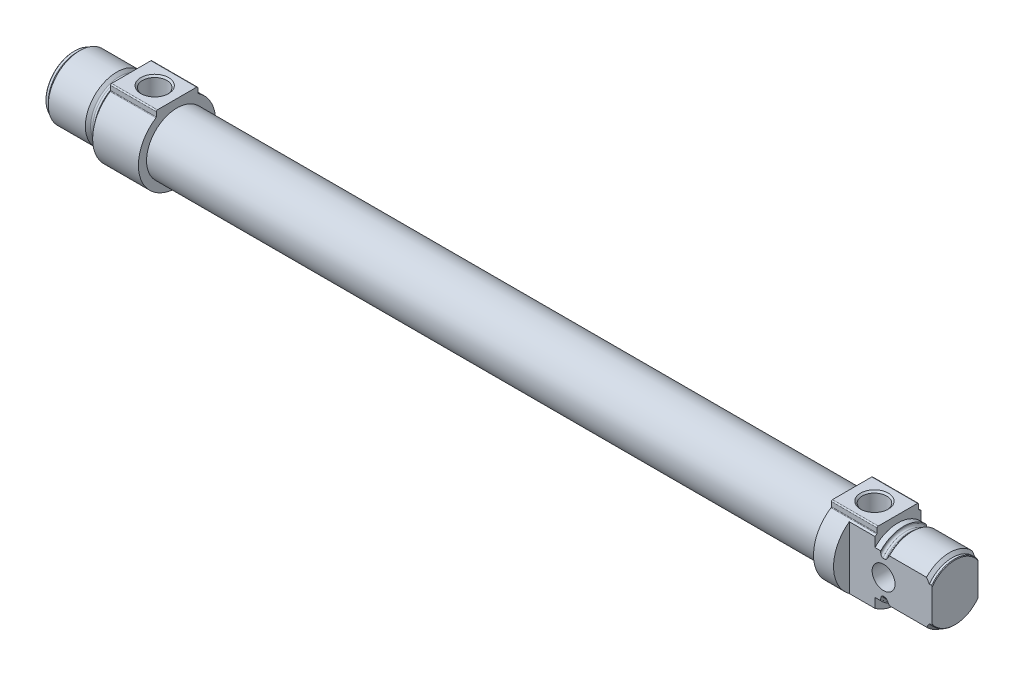
SolidWorks part; units mm, degrees
ref_plane "Ebene vorne" through (0, 0, 0) normal (0, 0, 1) x (1, 0, 0)
ref_plane "Ebene oben" through (0, 0, 0) normal (0, 1, 0) x (1, 0, 0)
ref_plane "Ebene rechts" through (0, 0, 0) normal (1, 0, 0) x (0, 0, -1)
sketch "Skizze1" plane through (0, 0, 0) normal (0, 0, 1) x (1, 0, 0)
  line L0 (0, 0) -> (0, 9.8)
  line L1 (0, 9.8) -> (0.2, 10)
  line L2 (0.2, 10) -> (1, 10)
  line L3 (1, 10) -> (2, 11)
  line L4 (2, 11) -> (14.95, 11)
  line L5 (14.95, 11) -> (15.8657, 10.0843)
  line L6 (16.4314, 9.85) -> (17.2, 9.85)
  line L7 (18, 10.65) -> (18, 11)
  line L8 (18, 11) -> (20, 11)
  line L9 (20, 11) -> (20, 0)
  line L10 (20, 0) -> (0, 0)
  line L11 (20, 0) -> (0, 0) construction
  arc A0 (15.8657, 10.0843) -> (16.4314, 9.85) centre (16.4314, 10.65) ccw
  arc A1 (17.2, 9.85) -> (18, 10.65) centre (17.2, 10.65) ccw
revolve "Rotation1" add sketch "Skizze1" angle 360 about L11 reverse direction yes
cosmetic thread "Gewindedarstellung1" parameters "D1"=13.87, "D2"=20.16
ref_plane "Ebene1" through (28.7, 0, 0) normal (1, 0, 0) x (0, 0, -1)
ref_plane "Ebene2" through (10.5, 0, 0) normal (1, 0, 0) x (0, 0, -1)
ref_plane "Ebene3" through (0, -14, 0) normal (0, 1, 0) x (1, 0, 0)
ref_plane "Ebene4" through (0, 13, 0) normal (0, 1, 0) x (1, 0, 0)
ref_plane "Ebene5" through (0, 0, 0) normal (0, 1, 0) x (1, 0, 0)
ref_plane "Ebene6" through (0, 0, 0) normal (0, 1, 0) x (1, 0, 0)
ref_plane "Ebene7" through (20, 0, 0) normal (1, 0, 0) x (0, 0, -1)
ref_plane "Ebene8" through (20, 0, 0) normal (1, 0, 0) x (0, 0, -1)
ref_plane "Ebene9" through (33, 0, 0) normal (1, 0, 0) x (0, 0, -1)
ref_plane "Ebene10" through (24.5, 0, 0) normal (1, 0, 0) x (0, 0, -1)
ref_plane "Ebene11" through (44.5, 0, 0) normal (1, 0, 0) x (0, 0, -1)
sketch "Skizze2" plane through (20, 0, 0) normal (1, 0, 0) x (0, 0, -1)
  line L0 (7.25, 11.5515) -> (7.25, 13.1)
  line L1 (6.85, 13.5) -> (-6.85, 13.5)
  line L2 (-7.25, 13.1) -> (-7.25, 11.5515)
  arc A0 (-7.3859, 11.3004) -> (7.3859, 11.3004) centre (0, 0) ccw
  arc A1 (7.3859, 11.3004) -> (7.25, 11.5515) centre (7.55, 11.5515) cw
  arc A2 (7.25, 13.1) -> (6.85, 13.5) centre (6.85, 13.1) ccw
  arc A3 (-6.85, 13.5) -> (-7.25, 13.1) centre (-6.85, 13.1) ccw
  arc A4 (-7.25, 11.5515) -> (-7.3859, 11.3004) centre (-7.55, 11.5515) cw
extrude "Aufsatz-Linear austragen1" add sketch "Skizze2" along normal blind 16
ref_plane "Ebene12" through (32.5, 0, 0) normal (1, 0, 0) x (0, 0, -1)
ref_plane "Ebene13" through (0, 0, 0) normal (0, 0, 1) x (1, 0, 0)
ref_plane "Ebene14" through (0, 0, -8.5) normal (0, 0, 1) x (1, 0, 0)
ref_plane "Ebene15" through (0, 0, 0) normal (0, 1, 0) x (1, 0, 0)
ref_plane "Ebene16" through (0, 6.9, 0) normal (0, 1, 0) x (1, 0, 0)
ref_plane "Ebene17" through (0, 0, -6.6) normal (0, 0, 1) x (1, 0, 0)
ref_plane "Ebene18" through (0, 0, 0) normal (0, 1, 0) x (1, 0, 0)
ref_plane "Ebene19" through (0, 6.9, 0) normal (0, 1, 0) x (1, 0, 0)
ref_plane "Ebene20" through (0, 7.8206, -1.379) normal (0, 0.9848, -0.1736) x (1, 0, 0)
ref_plane "Ebene21" through (0, 6.3434, -1.1185) normal (0, 0.9848, -0.1736) x (1, 0, 0)
sketch "Skizze3" plane through (0, 0, 0) normal (0, 0, 1) x (1, 0, 0)
  line L0 (36, 0) -> (36, 10.65)
  line L1 (36, 10.65) -> (272, 10.65)
  line L2 (272, 10.65) -> (272, 0)
  line L3 (272, 0) -> (36, 0)
  line L4 (272, 0) -> (36, 0) construction
revolve "Rotation2" add sketch "Skizze3" angle 360 about L4 reverse direction yes
ref_plane "Ebene22" through (272, 0, 0) normal (1, 0, 0) x (0, 0, -1)
sketch "Skizze4" plane through (272, 0, 0) normal (1, 0, 0) x (0, 0, -1)
  line L0 (7.25, 11.5515) -> (7.25, 13.1)
  line L1 (6.85, 13.5) -> (-6.85, 13.5)
  line L2 (-7.25, 13.1) -> (-7.25, 11.5515)
  arc A0 (-7.3859, 11.3004) -> (7.3859, 11.3004) centre (0, 0) ccw
  arc A1 (7.3859, 11.3004) -> (7.25, 11.5515) centre (7.55, 11.5515) cw
  arc A2 (7.25, 13.1) -> (6.85, 13.5) centre (6.85, 13.1) ccw
  arc A3 (-6.85, 13.5) -> (-7.25, 13.1) centre (-6.85, 13.1) ccw
  arc A4 (-7.25, 11.5515) -> (-7.3859, 11.3004) centre (-7.55, 11.5515) cw
extrude "Aufsatz-Linear austragen2" add sketch "Skizze4" along normal blind 16
ref_plane "Ebene23" through (275.8, 0, 0) normal (1, 0, 0) x (0, 0, -1)
ref_plane "Ebene24" through (275.5, 0, 0) normal (1, 0, 0) x (0, 0, -1)
ref_plane "Ebene25" through (0, 0, 6.6) normal (0, 0, 1) x (1, 0, 0)
ref_plane "Ebene26" through (0, 0, 0) normal (0, 1, 0) x (1, 0, 0)
ref_plane "Ebene27" through (0, 6.9, 0) normal (0, 1, 0) x (1, 0, 0)
ref_plane "Ebene28" through (0, 7.8206, 1.379) normal (0, 0.9848, 0.1736) x (1, 0, 0)
ref_plane "Ebene29" through (0, 6.3434, 1.1185) normal (0, 0.9848, 0.1736) x (1, 0, 0)
ref_plane "Ebene30" through (335, 0, 0) normal (1, 0, 0) x (0, 0, -1)
sketch "Skizze5" plane through (0, 0, 0) normal (0, 0, 1) x (1, 0, 0)
  line L0 (288, 0) -> (288, 11)
  line L1 (288, 11) -> (290, 11)
  line L2 (290, 11) -> (290, 10.65)
  line L3 (290.8, 9.85) -> (291.5686, 9.85)
  line L4 (292.1343, 10.0843) -> (293.05, 11)
  line L5 (293.05, 11) -> (306, 11)
  line L6 (306, 11) -> (307, 10)
  line L7 (307, 10) -> (307.8, 10)
  line L8 (307.8, 10) -> (308, 9.8)
  line L9 (308, 9.8) -> (308, 0)
  line L10 (308, 0) -> (288, 0)
  line L11 (308, 0) -> (288, 0) construction
  arc A0 (290, 10.65) -> (290.8, 9.85) centre (290.8, 10.65) ccw
  arc A1 (291.5686, 9.85) -> (292.1343, 10.0843) centre (291.5686, 10.65) ccw
revolve "Rotation3" add sketch "Skizze5" angle 360 about L11 reverse direction yes
cosmetic thread "Gewindedarstellung2" parameters "D1"=12.87, "D2"=20.16
ref_plane "Ebene31" through (322, 0, 0) normal (1, 0, 0) x (0, 0, -1)
ref_plane "Ebene32" through (330.5, 0, 0) normal (1, 0, 0) x (0, 0, -1)
ref_plane "Ebene33" through (310.5, 0, 0) normal (1, 0, 0) x (0, 0, -1)
sketch "Skizze6" plane through (0, 0, 0) normal (0, 1, 0) x (1, 0, 0)
  line L0 (279, 24) -> (279, 8)
  line L1 (279, 8) -> (308, 8)
  line L2 (308, 8) -> (308, -8)
  line L3 (308, -8) -> (279, -8)
  line L4 (279, -8) -> (279, -24)
  line L5 (279, -24) -> (324, -24)
  line L6 (324, -24) -> (324, 24)
  line L7 (324, 24) -> (279, 24)
extrude "Schnitt-Linear austragen1" cut sketch "Skizze6" along normal blind 13.5 and the other way blind 13.5
ref_plane "Ebene34" through (291, 0, 0) normal (1, 0, 0) x (0, 0, -1)
hole_wizard "Bohrung1" positions "Skizze8" profile "Skizze7" legacy
sketch "Skizze8" plane through (0, 0, -8) normal (0, 0, -1) x (-1, 0, 0)
  point P0 (-291, 0)
sketch "Skizze7" plane through (291, 0, -8) normal (1, 0, 0) x (0, 1, 0)
  line L0 (0, 0) -> (0, 16)
  line L1 (0, 16) -> (4, 16)
  line L2 (4, 16) -> (4, 0)
  line L3 (4, 0) -> (0, 0)
  line L4 (0, 110) -> (0, -10) construction
  dimension "Durchmesser" = 8
  dimension "Tiefe" = 16
hole_wizard "Bohrung2" positions "Skizze10" profile "Skizze9" legacy
sketch "Skizze10" plane through (0, 13.5, 0) normal (0, 1, 0) x (1, 0, 0)
  point P0 (28.2, 0)
sketch "Skizze9" plane through (28.2, 13.5, 0) normal (1, 0, 0) x (0, 0, 1)
  line L0 (0, 0) -> (0, 13.5)
  line L1 (0, 13.5) -> (4.283, 13.5)
  line L2 (4.283, 13.5) -> (4.283, 0.581)
  line L3 (4.283, 0.581) -> (4.864, 0)
  line L4 (4.864, 0) -> (0, 0)
  line L5 (0, -6.4453) -> (0, 115.525) construction
  line L6 (-4.283, 0.581) -> (-4.864, 0) construction
  dimension "Durchmesser" = 8.566
  dimension "Tiefe" = 13.5
  dimension "Senkwinkel1" = 90
  dimension "Senkdurchmesser3" = 9.728
cosmetic thread "Gewindedarstellung3" parameters "D1"=9.5, "D2"=9.728
hole_wizard "Bohrung3" positions "Skizze12" profile "Skizze11" legacy
sketch "Skizze12" plane through (0, 13.5, 0) normal (0, 1, 0) x (1, 0, 0)
  point P0 (279.8, 0)
sketch "Skizze11" plane through (279.8, 13.5, 0) normal (1, 0, 0) x (0, 0, 1)
  line L0 (0, 0) -> (0, 18.4728)
  line L1 (0, 18.4728) -> (4.283, 16)
  line L2 (4.283, 16) -> (4.283, 0.581)
  line L3 (4.283, 0.581) -> (4.864, 0)
  line L4 (4.864, 0) -> (0, 0)
  line L5 (0, -14.3089) -> (0, 102.4216) construction
  line L6 (0, 18.4728) -> (-4.283, 16) construction
  line L7 (-4.283, 0.581) -> (-4.864, 0) construction
  dimension "Durchmesser" = 8.566
  dimension "Tiefe" = 16
  dimension "Senkdurchmesser1" = 9.728
  dimension "Senkwinkel1" = 90
  dimension "Spitzenwinkel" = 120
cosmetic thread "Gewindedarstellung4" parameters "D1"=8, "D2"=9.728
sketch "Skizze13" plane through (0, 0, 0) normal (0, 0, 1) x (1, 0, 0)
  line L0 (-4, 0) -> (-4, 4)
  line L1 (-4, 4) -> (50.3, 4)
  line L2 (50.3, 4) -> (50.3, 10)
  line L3 (50.3, 10) -> (255.3, 10)
  line L4 (255.3, 10) -> (255.3, 0)
  line L5 (255.3, 0) -> (-4, 0)
  line L6 (255.3, 0) -> (-4, 0) construction
revolve "Schnitt-Rotation1" cut sketch "Skizze13" angle 360 about L6 reverse direction yes
ref_plane "Ebene35" through (-4, 0, 0) normal (1, 0, 0) x (0, 0, -1)
ref_plane "Ebene36" through (0, 13.5, 0) normal (0, 1, 0) x (1, 0, 0)
ref_plane "Ebene37" through (6.5, 0, 0) normal (1, 0, 0) x (0, 0, -1)
ref_plane "Ebene38" through (0, 0, 0) normal (1, 0, 0) x (0, 0, -1)
ref_plane "Ebene39" through (20, 0, 0) normal (1, 0, 0) x (0, 0, -1)
ref_plane "Ebene40" through (288, 0, 0) normal (1, 0, 0) x (0, 0, -1)
ref_plane "Ebene41" through (20, 0, 0) normal (1, 0, 0) x (0, 0, -1)
ref_plane "Ebene42" through (0, 13.5, 0) normal (0, 1, 0) x (1, 0, 0)
ref_plane "Ebene43" through (45.5, 0, 0) normal (1, 0, 0) x (0, 0, -1)
ref_plane "Ebene44" through (262.5, 0, 0) normal (1, 0, 0) x (0, 0, -1)
ref_plane "Ebene45" through (0, 0, 0) normal (0, 0, 1) x (1, 0, 0)
ref_plane "Ebene46" through (20, 0, 0) normal (1, 0, 0) x (0, 0, -1)
ref_plane "Ebene47" through (0, 13.5, 0) normal (0, 1, 0) x (1, 0, 0)
ref_plane "FDT_FRONT XY" through (20, 0, 0) normal (1, 0, 0) x (0, 0, -1)
ref_plane "FDT_FRONT XZ" through (0, 0, 0) normal (0, -1, 0) x (-1, 0, 0)
ref_plane "FDT_FRONT YZ" through (0, 0, 0) normal (0, 0, -1) x (-1, 0, 0)
ref_axis "FDT_FRONT X" through (20, 0, 80.9) along (0, 0, -1)
ref_axis "FDT_FRONT Y" through (20, -50, 0) along (0, 1, 0)
ref_axis "FDT_FRONT Z" through (80.9, 0, 0) along (-1, 0, 0)
sketch3d "FDT_FRONT"
  point P0 (20, 0, 0)
ref_plane "FDT_QSFRONT XY" through (0, 13.5, 0) normal (0, 1, 0) x (1, 0, 0)
ref_plane "FDT_QSFRONT XZ" through (28.2, 0, 0) normal (-1, 0, 0) x (0, 0, 1)
ref_plane "FDT_QSFRONT YZ" through (0, 0, 0) normal (0, 0, 1) x (1, 0, 0)
ref_axis "FDT_QSFRONT X" through (28.2, 13.5, -50) along (0, 0, 1)
ref_axis "FDT_QSFRONT Y" through (-80.9, 13.5, 0) along (1, 0, 0)
ref_axis "FDT_QSFRONT Z" through (28.2, 50, 0) along (0, -1, 0)
sketch3d "FDT_QSFRONT"
  point P0 (28.2, 13.5, 0)
ref_plane "FDT_QSREAR XY" through (0, 13.5, 0) normal (0, 1, 0) x (1, 0, 0)
ref_plane "FDT_QSREAR XZ" through (279.8, 0, 0) normal (-1, 0, 0) x (0, 0, 1)
ref_plane "FDT_QSREAR YZ" through (0, 0, 0) normal (0, 0, 1) x (1, 0, 0)
ref_axis "FDT_QSREAR X" through (279.8, 13.5, -50) along (0, 0, 1)
ref_axis "FDT_QSREAR Y" through (-80.9, 13.5, 0) along (1, 0, 0)
ref_axis "FDT_QSREAR Z" through (279.8, 50, 0) along (0, -1, 0)
sketch3d "FDT_QSREAR"
  point P0 (279.8, 13.5, 0)
ref_plane "FDT_REAR XY" through (288, 0, 0) normal (-1, 0, 0) x (0, 0, 1)
ref_plane "FDT_REAR XZ" through (0, 0, 0) normal (0, 1, 0) x (1, 0, 0)
ref_plane "FDT_REAR YZ" through (0, 0, 0) normal (0, 0, -1) x (-1, 0, 0)
ref_axis "FDT_REAR X" through (288, 0, 80.9) along (0, 0, -1)
ref_axis "FDT_REAR Y" through (288, 50, 0) along (0, -1, 0)
ref_axis "FDT_REAR Z" through (-80.9, 0, 0) along (1, 0, 0)
sketch3d "FDT_REAR"
  point P0 (288, 0, 0)
ref_plane "FDT_SMBR1 XY" through (45.5, 0, 0) normal (-1, 0, 0) x (0, 0, 1)
ref_plane "FDT_SMBR1 XZ" through (0, 0, 0) normal (0, -1, 0) x (-1, 0, 0)
ref_plane "FDT_SMBR1 YZ" through (0, 0, 0) normal (0, 0, 1) x (1, 0, 0)
ref_axis "FDT_SMBR1 X" through (45.5, 0, -80.9) along (0, 0, 1)
ref_axis "FDT_SMBR1 Y" through (45.5, -50, 0) along (0, 1, 0)
ref_axis "FDT_SMBR1 Z" through (-80.9, 0, 0) along (1, 0, 0)
sketch3d "FDT_SMBR1"
  point P0 (45.5, 0, 0)
ref_plane "FDT_SMBR2 XY" through (262.5, 0, 0) normal (-1, 0, 0) x (0, 0, 1)
ref_plane "FDT_SMBR2 XZ" through (0, 0, 0) normal (0, -1, 0) x (-1, 0, 0)
ref_plane "FDT_SMBR2 YZ" through (0, 0, 0) normal (0, 0, 1) x (1, 0, 0)
ref_axis "FDT_SMBR2 X" through (262.5, 0, -80.9) along (0, 0, 1)
ref_axis "FDT_SMBR2 Y" through (262.5, -50, 0) along (0, 1, 0)
ref_axis "FDT_SMBR2 Z" through (-80.9, 0, 0) along (1, 0, 0)
sketch3d "FDT_SMBR2"
  point P0 (262.5, 0, 0)
ref_plane "FDT_SWIVELAXIS XY" through (0, 0, 0) normal (0, 0, 1) x (1, 0, 0)
ref_plane "FDT_SWIVELAXIS XZ" through (0, 0, 0) normal (0, -1, 0) x (-1, 0, 0)
ref_plane "FDT_SWIVELAXIS YZ" through (291, 0, 0) normal (1, 0, 0) x (0, 0, -1)
ref_axis "FDT_SWIVELAXIS X" through (-80.9, 0, 0) along (1, 0, 0)
ref_axis "FDT_SWIVELAXIS Y" through (291, -50, 0) along (0, 1, 0)
ref_axis "FDT_SWIVELAXIS Z" through (291, 0, 80.9) along (0, 0, -1)
sketch3d "FDT_SWIVELAXIS"
  point P0 (291, 0, 0)
ref_plane "NUT XY" through (6.5, 0, 0) normal (1, 0, 0) x (0, 0, -1)
ref_plane "NUT XZ" through (0, 0, 0) normal (0, -1, 0) x (-1, 0, 0)
ref_plane "NUT YZ" through (0, 0, 0) normal (0, 0, -1) x (-1, 0, 0)
ref_axis "NUT X" through (6.5, 0, 80.9) along (0, 0, -1)
ref_axis "NUT Y" through (6.5, -50, 0) along (0, 1, 0)
ref_axis "NUT Z" through (80.9, 0, 0) along (-1, 0, 0)
sketch3d "NUT"
  point P0 (6.5, 0, 0)
ref_plane "ZR XY" through (0, 0, 0) normal (1, 0, 0) x (0, 0, -1)
ref_plane "ZR XZ" through (0, 0, 0) normal (0, -1, 0) x (-1, 0, 0)
ref_plane "ZR YZ" through (0, 0, 0) normal (0, 0, -1) x (-1, 0, 0)
ref_axis "ZR X" through (0, 0, 80.9) along (0, 0, -1)
ref_axis "ZR Y" through (0, -50, 0) along (0, 1, 0)
ref_axis "ZR Z" through (80.9, 0, 0) along (-1, 0, 0)
sketch3d "ZR"
  point P0 (0, 0, 0)
ref_plane "ZYL XY" through (20, 0, 0) normal (1, 0, 0) x (0, 0, -1)
ref_plane "ZYL XZ" through (0, 0, 0) normal (0, -1, 0) x (-1, 0, 0)
ref_plane "ZYL YZ" through (0, 0, 0) normal (0, 0, -1) x (-1, 0, 0)
ref_axis "ZYL X" through (20, 0, 80.9) along (0, 0, -1)
ref_axis "ZYL Y" through (20, -50, 0) along (0, 1, 0)
ref_axis "ZYL Z" through (80.9, 0, 0) along (-1, 0, 0)
sketch3d "ZYL"
  point P0 (20, 0, 0)
